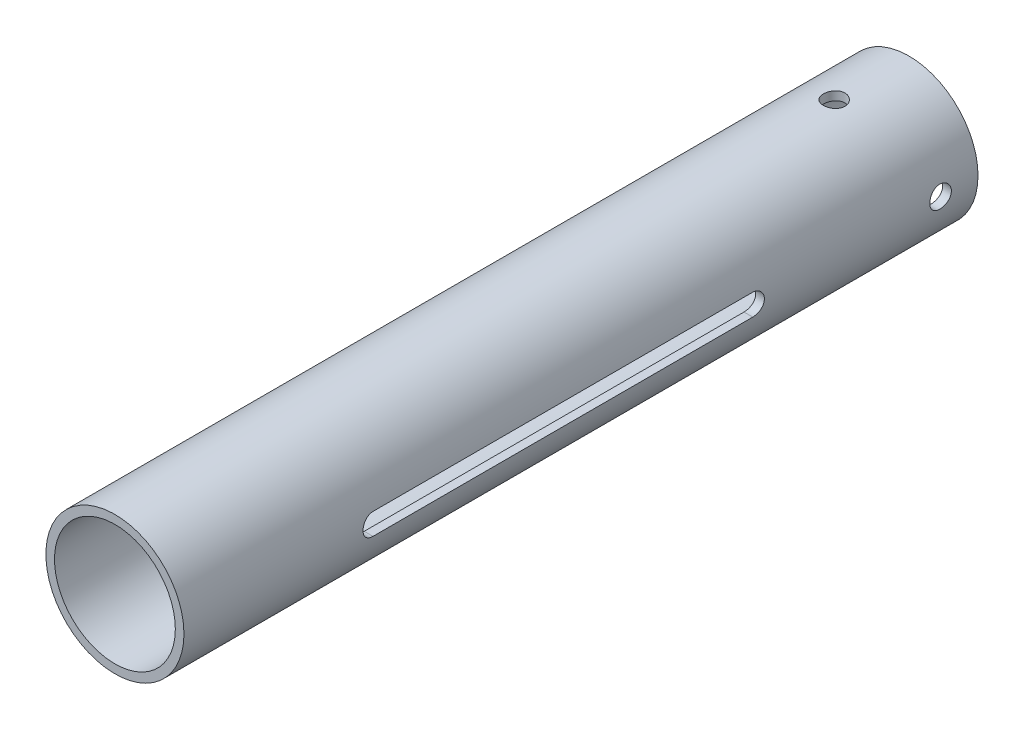
SolidWorks part; units mm, degrees
ref_plane "Front Plane" through (0, 0, 0) normal (0, 0, 1) x (1, 0, 0)
ref_plane "Top Plane" through (0, 0, 0) normal (0, 1, 0) x (1, 0, 0)
ref_plane "Right Plane" through (0, 0, 0) normal (1, 0, 0) x (0, 0, -1)
sketch "Sketch1" plane through (0, 0, 0) normal (0, 0, 1) x (1, 0, 0)
  line L0 (-25.4, 0) -> (-22.225, 0) construction
  circle A0 centre (0, 0) radius 22.225 construction
  circle A1 centre (0, 0) radius 25.4 construction
  dimension "OD" = 50.8
  dimension "ID" = 44.45
  dimension "Wall Thickness" = 3.175
sketch "Sketch2" plane through (0, 0, 0) normal (1, 0, 0) x (0, 0, -1)
  line L0 (-152.4, -25.4) -> (152.4, -25.4) construction
  point P2 (0, -25.4)
  point P3 (76.2, -25.4)
  point P4 (-76.2, -25.4)
  dimension "Length" = 304.8
  dimension "D1" = 76.2
  dimension "D2" = 76.2
sketch "Sketch3" plane through (0, 0, 0) normal (0, 0, 1) x (1, 0, 0)
  circle A0 centre (0, 0) radius 22.225 construction
  circle A1 centre (0, 0) radius 25.4 construction
  circle A2 centre (0, 0) radius 22.225
  circle A3 centre (0, 0) radius 25.4
extrude "Boss-Extrude2" add sketch "Sketch3" along normal up to vertex (152.4 mm away) and the other way up to vertex (152.4 mm away) up to point (0, -25.4, 152.4) other way up to point (0, -25.4, -152.4)
sketch "Sketch4" plane through (0, 0, 152.4) normal (0, 0, 1) x (1, 0, 0)
  circle A0 centre (0, 0) radius 36.4857
extrude "Cut-Extrude1" cut sketch "Sketch4" against normal offset from surface (12.7 mm away) 12.7 up to face at (25.4, 0, 152.4)
sketch "Sketch5" plane through (0, 0, 0) normal (1, 0, 0) x (0, 0, -1)
  line L0 (0, 0) -> (69.85, 0) construction
  line L1 (0, 0) -> (-69.85, 0) construction
  line L2 (-139.7, 0) -> (152.4, 0) construction
  line L3 (152.4, -25.4) -> (152.4, 25.4) construction
  line L4 (-139.7, 25.4) -> (-139.7, -25.4) construction
  line L5 (-69.85, 3.9687) -> (69.85, 3.9687)
  line L6 (69.85, -3.9687) -> (-69.85, -3.9687)
  line L7 (0, 3.9687) -> (0, -3.9687) construction
  circle A0 centre (-69.85, 0) radius 3.9687 construction
  arc A2 (-69.85, 3.9687) -> (-69.85, -3.9687) centre (-69.85, 0) ccw
  circle A4 centre (69.85, 0) radius 3.9688 construction
  arc A5 (69.85, 3.9687) -> (69.85, -3.9687) centre (69.85, 0) cw
  point P13 (0, 3.9687)
  point P14 (0, -3.9687)
  point P17 (0, 0)
  dimension "D1" = 69.85
  dimension "D2" = 82.55
  dimension "D3" = 7.9375
extrude "Cut-Extrude2" cut sketch "Sketch5" against normal through all both and the other way through all
sketch "Sketch6" plane through (0, 0, 0) normal (1, 0, 0) x (0, 0, -1)
  line L0 (152.4, -25.4) -> (152.4, 25.4) construction
  line L1 (111.125, 0) -> (124.8833, 0) construction
  line L2 (124.8833, 0) -> (138.6417, 0) construction
  line L3 (138.6417, 0) -> (152.4, 0) construction
  circle A0 centre (138.6417, 0) radius 3.9687
  point P0 (111.125, 0)
  point P1 (124.8833, 0)
  point P2 (138.6417, 0)
  point P3 (152.4, 0)
  dimension "D2" = 7.9375
  dimension "D1" = 41.275
extrude "Cut-Extrude3" cut sketch "Sketch6" against normal through all both and the other way through all
sketch "Sketch8" plane through (0, 0, 0) normal (0, 1, 0) x (1, 0, 0)
  line L1 (0, 111.125) -> (0, 124.8833) construction
  line L2 (0, 124.8833) -> (0, 138.6417) construction
  line L3 (0, 138.6417) -> (0, 152.4) construction
  line L4 (25.4, 152.4) -> (-25.4, 152.4) construction
  circle A1 centre (0, 124.8833) radius 3.9688
  point P0 (0, 111.125)
  point P1 (0, 124.8833)
  point P2 (0, 138.6417)
  point P3 (0, 152.4)
  dimension "D2" = 7.9375
  dimension "D1" = 41.275
extrude "Cut-Extrude4" cut sketch "Sketch8" against normal through all both and the other way through all
equation "\"D1@Sketch2\"=\"OD@Sketch1\"*1.5"
equation "\"D2@Sketch2\"=\"D1@Sketch2\""
